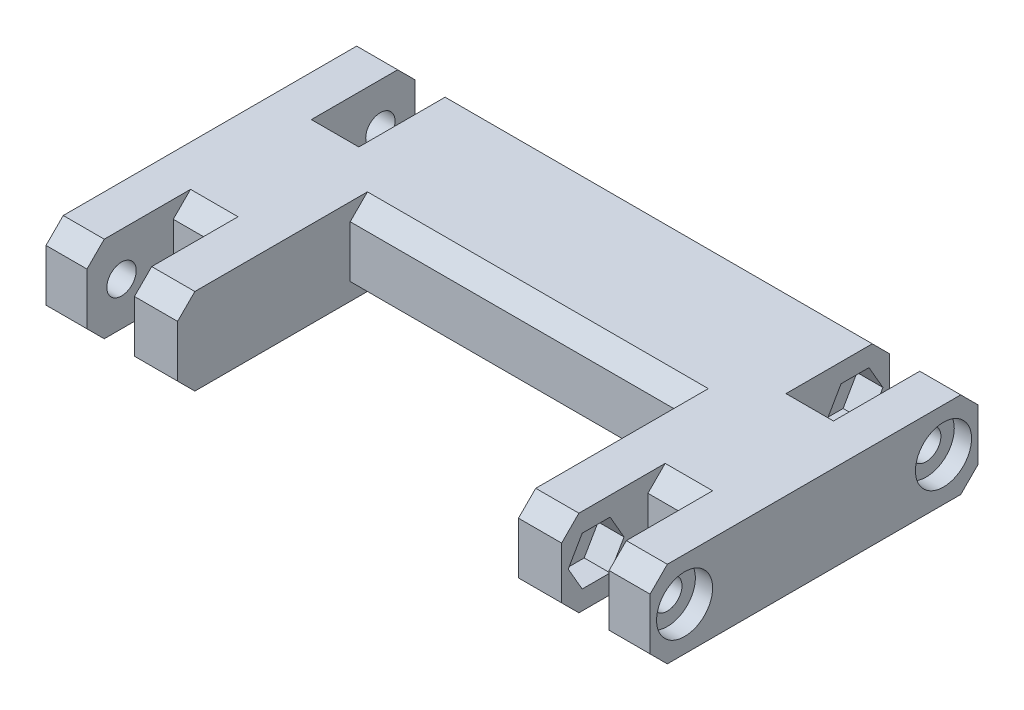
SolidWorks part; units mm, degrees
ref_plane "Front Plane" through (0, 0, 0) normal (0, 0, 1) x (1, 0, 0)
ref_plane "Top Plane" through (0, 0, 0) normal (0, 1, 0) x (1, 0, 0)
ref_plane "Right Plane" through (0, 0, 0) normal (1, 0, 0) x (0, 0, -1)
sketch "Sketch1" plane through (0, 0, 0) normal (0, 1, 0) x (1, 0, 0)
  line L1 (-35, -19) -> (35, -19)
  line L2 (-35, -19) -> (-35, 19)
  line L3 (-35, 19) -> (35, 19)
  line L4 (35, -19) -> (35, 19)
  line L5 (-35, -19) -> (35, 19) construction
  line L6 (-35, 19) -> (35, -19) construction
  point P0 (0, 0)
  dimension "D1" = 70
  dimension "D2" = 38
extrude "Boss-Extrude1" add sketch "Sketch1" along normal blind 10
sketch "Sketch2" plane through (0, 10, 0) normal (0, 1, 0) x (1, 0, 0)
  line L0 (35, 19) -> (-35, 19) construction
  line L1 (-30.25, 19) -> (-24.75, 19)
  line L2 (-30.25, 19) -> (-30.25, 9)
  line L3 (-30.25, 9) -> (-24.75, 9)
  line L4 (-24.75, 19) -> (-24.75, 9)
  line L5 (0, 0) -> (0, 19) construction
  line L6 (24.75, 19) -> (24.75, 9)
  line L7 (30.25, 9) -> (24.75, 9)
  line L8 (30.25, 19) -> (30.25, 9)
  line L9 (30.25, 19) -> (24.75, 19)
  dimension "D1" = 5.5
  dimension "D2" = 10
  dimension "D3" = 49.5
extrude "Cut-Extrude1" cut sketch "Sketch2" against normal through all
hole_wizard "CBORE for M3 Cheese Head Screw1" positions "Sketch7" profile "Sketch8" counterbore size "M3" standard "ISO" end condition up to next
sketch "Sketch7" plane through (35, 0, 0) normal (1, 0, 0) x (0, 0, -1)
  line L0 (-19, 10) -> (19, 10) construction
  line L1 (19, 10) -> (19, 0) construction
  point P0 (15, 5)
  dimension "D1" = 5
  dimension "D2" = 4
sketch "Sketch8" plane through (35, 5, -15) normal (0, 1, 0) x (0, 0, -1)
  line L0 (0, 0) -> (0, 56.75)
  line L1 (0, 56.75) -> (1.7, 56.75)
  line L3 (1.7, 56.75) -> (1.7, 2)
  line L4 (1.7, 2) -> (3.25, 2)
  line L5 (3.25, 2) -> (3.25, 0)
  line L7 (3.25, 0) -> (0, 0)
  line L11 (0, -6.35) -> (0, 107.95) construction
  dimension "Thru Hole Dia." = 3.4
  dimension "Thru Hole Depth" = 56.75
  dimension "C'Bore Dia." = 6.5
  dimension "C'Bore Depth" = 2
sketch "Sketch9" plane through (24.75, 0, 0) normal (1, 0, 0) x (0, 0, -1)
  line L1 (16.6166, 7.8) -> (13.3834, 7.8)
  line L2 (13.3834, 7.8) -> (11.7668, 5)
  line L3 (11.7668, 5) -> (13.3834, 2.2)
  line L4 (13.3834, 2.2) -> (16.6166, 2.2)
  line L5 (16.6166, 2.2) -> (18.2332, 5)
  line L6 (18.2332, 5) -> (16.6166, 7.8)
  circle A0 centre (15, 5) radius 2.8 construction
  dimension "D1" = 5.6
extrude "Cut-Extrude2" cut sketch "Sketch9" against normal blind 3
mirror "Mirror1" about plane through (0, 0, 0) normal (1, 0, 0) of "Cut-Extrude2", "CBORE for M3 Cheese Head Screw1"
mirror "Mirror2" about plane through (0, 0, 0) normal (0, 0, 1) of "Cut-Extrude1", "CBORE for M3 Cheese Head Screw1", "Cut-Extrude2", "Mirror1"
chamfer "Chamfer1" distance 2 angle 45 12 edges at (32.625, 0, -19) (32.625, 10, -19) (0, 0, -19) (0, 10, -19) (-32.625, 0, -19) (-32.625, 10, -19) (-32.625, 0, 19) (32.625, 0, 19) (0, 0, 19) (32.625, 10, 19) (-32.625, 10, 19) (0, 10, 19)
sketch "Sketch10" plane through (0, 10, 0) normal (0, 1, 0) x (1, 0, 0)
  line L0 (0, 0) -> (0, -19) construction
  line L1 (24.75, -19) -> (-24.75, -19) construction
  line L2 (-24.75, -9) -> (-24.75, -17) construction
  line L3 (-19.75, -19) -> (19.75, -19)
  line L4 (-19.75, -19) -> (-19.75, 1)
  line L5 (-19.75, 1) -> (19.75, 1)
  line L6 (19.75, -19) -> (19.75, 1)
  line L7 (-19.75, -19) -> (19.75, 1) construction
  line L8 (-19.75, 1) -> (19.75, -19) construction
  point P5 (0, -9)
  dimension "D1" = 5
  dimension "D2" = 20
extrude "Cut-Extrude3" cut sketch "Sketch10" against normal through all
chamfer "Chamfer2" distance 2 angle 45 2 edges at (0, 0, -1) (0, 10, -1)
chamfer "Chamfer3" distance 2 angle 45 8 edges at (27.5, 0, -9) (27.5, 10, -9) (27.5, 10, 9) (27.5, 0, 9) (-27.5, 10, 9) (-27.5, 0, 9) (-27.5, 0, -9) (-27.5, 10, -9)
